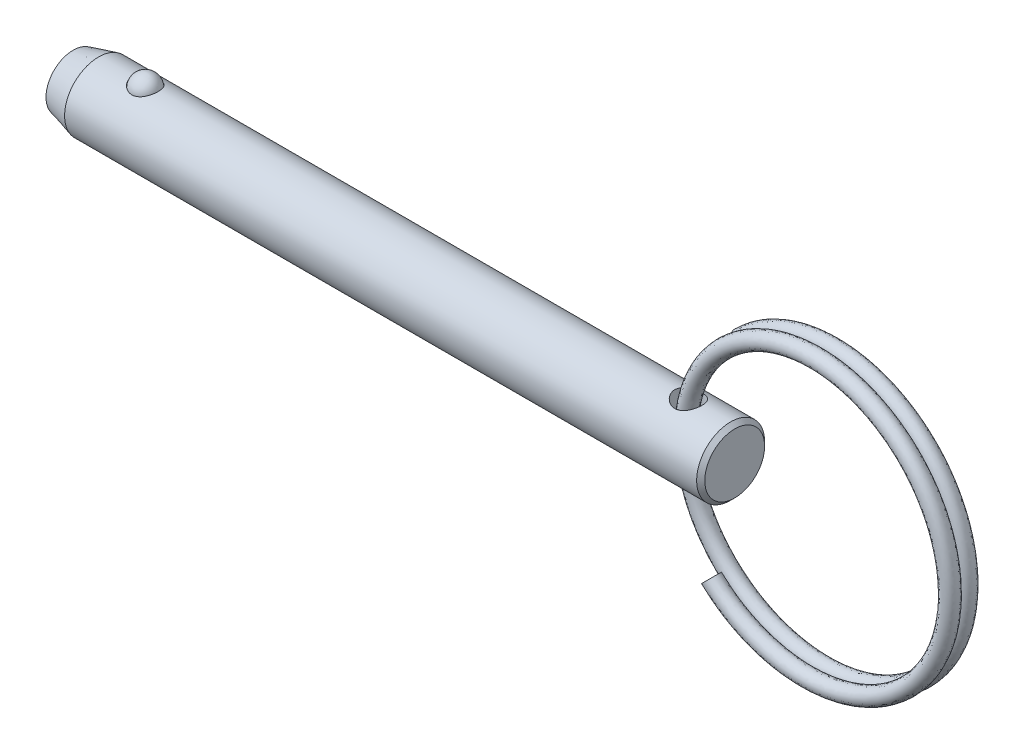
SolidWorks part; units mm, degrees
note: The reader was unsure of these and kept them because the rebuilt part matched: shared geometry of "Sketch6<2>".
ref_plane "Front" through (0, 0, 0) normal (0, 0, 1) x (1, 0, 0)
ref_plane "Top" through (0, 0, 0) normal (0, 1, 0) x (1, 0, 0)
ref_plane "Right" through (0, 0, 0) normal (1, 0, 0) x (0, 0, -1)
sketch "Sketch1" plane through (0, 0, 0) normal (0, 0, 1) x (1, 0, 0)
  line L0 (30.8864, 2.794) -> (30.5054, 3.175)
  line L1 (30.5054, 3.175) -> (30.8864, 3.175) construction
  line L4 (30.8864, 2.794) -> (30.8864, 0)
  line L5 (30.8864, 3.175) -> (30.8864, 2.794) construction
  line L16 (30.5054, 3.175) -> (-28.5165, 3.175)
  line L17 (-30.8864, 3.175) -> (-30.8864, 2.54) construction
  line L19 (-28.5165, 3.175) -> (-30.8864, 3.175) construction
  line L22 (-30.8864, -3.175) -> (-28.5165, -3.175) construction
  line L23 (-24.1519, 2.8575) -> (-24.1519, -2.8575) construction
  line L24 (-30.8864, 0) -> (30.8864, 0)
  line L27 (30.8864, 0) -> (33.6804, 0) construction
  line L29 (-30.8864, 0) -> (-30.8864, -2.54) construction
  line L36 (25.2984, 0) -> (25.2984, 3.175) construction
  line L37 (-30.8864, 2.54) -> (-30.8864, 0)
  line L38 (-28.5165, -3.175) -> (30.8864, -3.175) construction
  line L39 (-30.8864, -2.54) -> (-30.8864, -3.175) construction
  line L40 (-28.5165, 3.175) -> (-30.8864, 2.54)
  line L42 (-28.5165, -3.175) -> (-30.8864, -2.54) construction
  line L43 (-28.5165, 3.175) -> (-28.5165, -3.175) construction
  circle A2 centre (-24.1519, 2.8575) radius 1.2319 construction
  point P35 (-22.9616, 3.175)
  dimension "A1" = 15
revolve "Revolve1" add sketch "Sketch1" angle 360 about L27
sketch "Sketch2" plane through (0, 0, 0) normal (0, 0, 1) x (1, 0, 0)
  line L0 (-22.8946, 2.8575) -> (-25.4092, 2.8575)
  line L1 (-24.1519, 4.0894) -> (-24.1519, 4.1148) construction
  line L2 (-22.8946, 2.8575) -> (-20.38, 2.8575) construction
  circle A0 centre (-24.1519, 2.8575) radius 1.2319 construction
  circle A1 centre (-24.1519, 2.8575) radius 1.2319 construction
  arc A2 (-25.4092, 2.8575) -> (-22.8946, 2.8575) centre (-24.1519, 2.8575) cw
  dimension "D1" = 0.0254
revolve "Cut-Revolve1" cut sketch "Sketch2" angle 360 about L2
sketch "Sketch3" plane through (0, 0, 0) normal (0, 0, 1) x (1, 0, 0)
  line L0 (-22.92, 2.8575) -> (-25.3838, 2.8575)
  line L1 (-22.92, 2.8575) -> (-20.4562, 2.8575) construction
  circle A0 centre (-24.1519, 2.8575) radius 1.2319 construction
  arc A1 (-22.92, 2.8575) -> (-25.3838, 2.8575) centre (-24.1519, 2.8575) ccw
revolve "Revolve2" add sketch "Sketch3" angle 360 about L1
sketch "Sketch4" plane through (0, 0, 0) normal (0, 0, 1) x (1, 0, 0)
  line L1 (26.5684, -3.175) -> (27.8384, -3.175)
  line L2 (26.5684, -3.175) -> (26.5684, 3.175)
  line L3 (26.5684, 3.175) -> (27.8384, 3.175)
  line L4 (27.8384, -3.175) -> (27.8384, 3.175)
  line L5 (26.5684, -3.175) -> (26.5684, -4.445) construction
  line L6 (27.8384, 3.175) -> (30.8864, 3.175) construction
  line L8 (25.2984, -3.175) -> (25.2984, 3.175) construction
  line L9 (25.2984, 0) -> (26.5684, 0) construction
  line L11 (26.5684, 0) -> (27.8384, 0) construction
  line L12 (30.5054, 3.175) -> (-28.5165, 3.175) construction
  line L14 (-28.5165, -3.175) -> (30.8864, -3.175) construction
  dimension "D1" = 2.54
revolve "Cut-Revolve2" cut sketch "Sketch4" angle 360 about L2
sketch "Sketch5" plane through (0, 0, 0) normal (0, 0, 1) x (1, 0, 0)
  line L0 (0, 0) -> (25.5914, 0) construction
  line L1 (25.5914, 0) -> (25.5914, 3.175) construction
  line L2 (30.5054, 3.175) -> (-28.5165, 3.175) construction
  line L3 (39.0534, 0) -> (52.5154, 0) construction
  line L4 (27.8384, 3.175) -> (27.5454, 3.175) construction
  line L5 (26.5684, 3.175) -> (27.8384, 3.175) construction
  line L6 (25.9712, 3.175) -> (25.9712, -3.175) construction
  line L7 (25.5914, 3.175) -> (25.2984, 3.175) construction
  line L8 (26.5684, -3.175) -> (27.8384, -3.175) construction
  line L9 (25.9712, -3.175) -> (27.8384, -3.175) construction
  line L10 (25.5914, 0) -> (39.0534, 0) construction
  line L12 (27.5454, 3.175) -> (25.9712, 3.175) construction
  line L13 (39.0534, 11.938) -> (39.0534, 13.462) construction
  circle A0 centre (39.0534, 0) radius 13.462
  circle A1 centre (39.0534, 0) radius 11.938 construction
  circle A2 centre (39.0534, 0) radius 12.7 construction
  point P26 (39.0534, 12.7)
curve "Helix/Spiral1" pitch 1.5494 height 1.3557 radius 13.462 left hand yes centre (39.0534, 0, 0) axis (0, 0, -1) start towards (1, 0, 0)
sketch "Sketch6" plane through (114.0038, 0, 0) normal (0, 1, 0) x (0, 0, -1)
  line L0 (0, 86.8884) -> (0, 87.6504) construction
  line L1 (0, 87.6504) -> (0, 88.4124) construction
  circle A0 centre (0, 87.6504) radius 0.762
  dimension "D1" = 1.524
sketch "Sketch7" plane through (0, 0, 0) normal (0, 0, 1) x (1, 0, 0)
  circle A0 centre (39.0534, 0) radius 13.462 construction
  circle A1 centre (39.0534, 0) radius 13.462
curve "Helix/Spiral2" pitch 1.5494 height 1.3557 radius 13.462 left hand yes centre (39.0534, 0, 0) axis (0, 0, 1) start towards (1, 0, 0)
sweep "Sweep1" add profiles "Sketch6" path "Helix/Spiral1"
sweep "Sweep2" add profiles "Sketch6<2>" path "Helix/Spiral2"
sketch "Sketch6<2>" plane through (114.0038, 0, 0) normal (0, 1, 0) x (0, 0, -1) same geometry as "Sketch6"
equation "\"D12@Sketch1\"=\"A@Sketch1\" * 0.80"
equation "\"D2@Sketch1\"=\"A@Sketch1\" * 0.9"
equation "\"D1@Sketch4\" = \"A@Sketch1\" / 2.5"
equation "\"Ring OD@Sketch5\" = \"R Ring Dia@Sketch5\" * 0.06"
equation "\"D4@Helix/Spiral1\"=\"Ring OD@Sketch5\" + 0.001"
equation "\"D1@Sketch6\"=\"Ring OD@Sketch5\""
equation "\"D4@Helix/Spiral2\" = \"D4@Helix/Spiral1\""
equation "\"D5@Helix/Spiral2\" = \"D5@Helix/Spiral1\""
